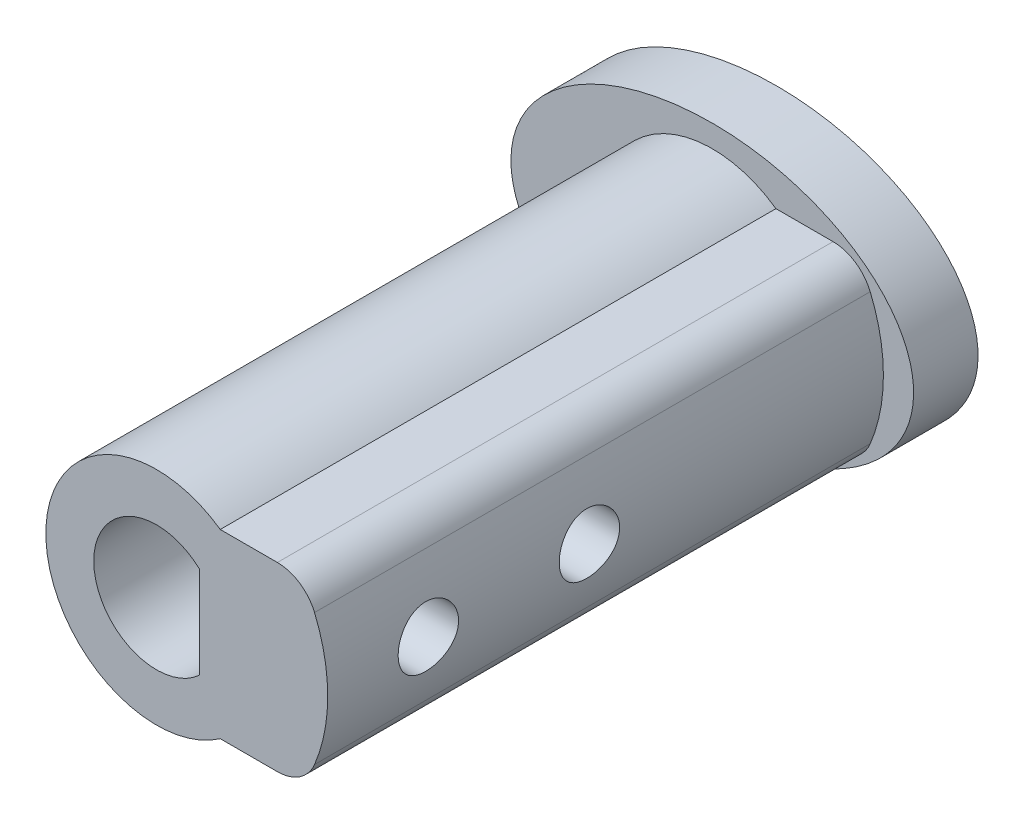
SolidWorks part; units mm, degrees
ref_plane "Front Plane" through (0, 0, 0) normal (0, 0, 1) x (1, 0, 0)
ref_plane "Top Plane" through (0, 0, 0) normal (0, 1, 0) x (1, 0, 0)
ref_plane "Right Plane" through (0, 0, 0) normal (1, 0, 0) x (0, 0, -1)
sketch "Sketch1" plane through (0, 0, 0) normal (0, 0, 1) x (1, 0, 0)
  line L7 (4.25, -2.25) -> (-4.25, -2.25)
  line L8 (4.25, -2.25) -> (4.25, 2.25)
  line L9 (4.25, 2.25) -> (-4.25, 2.25)
  line L10 (-4.25, -2.25) -> (-4.25, 2.25)
  line L11 (4.25, -2.25) -> (-4.25, 2.25) construction
  line L12 (4.25, 2.25) -> (-4.25, -2.25) construction
  circle A0 centre (0, 0) radius 2.75
  circle A1 centre (0, 0) radius 4.25
  dimension "D1" = 5.5
  dimension "D2" = 8.5
  dimension "D4" = 4.5
extrude "Boss-Extrude1" add sketch "Sketch1" along normal blind 13.8 contours A1 L9 A0 L7 | A0 region at (3.1989, 0, 0)
sketch "Sketch3" plane through (0, 0, 13.8) normal (0, 0, 1) x (1, 0, 0)
  line L0 (1, 1.118) -> (1, -1.118)
  circle A1 centre (0, 0) radius 1.5
  dimension "D1" = 3
  dimension "D2" = 1
extrude "Cut-Extrude1" cut sketch "Sketch3" against normal blind 8.3 contours L0 A1 region at (-0.148, 0, 13.8)
ref_plane "Plane1" through (4.25, 0, 0) normal (1, 0, 0) x (0, 0, -1)
sketch "Sketch5" plane through (4.25, 0, 0) normal (1, 0, 0) x (0, 0, -1)
  line L1 (-13.8, 2.25) -> (-13.8, -2.25) construction
  circle A0 centre (-11.3, 0) radius 0.75
  circle A1 centre (-7.3, 0) radius 0.75
  dimension "D1" = 1.5
  dimension "D2" = 1.5
  dimension "D3" = 2.5
  dimension "D4" = 6.5
extrude "Cut-Extrude3" cut sketch "Sketch5" against normal blind 4.5
sketch "Sketch4" plane through (0, 0, 0) normal (0, 0, -1) x (-1, 0, 0)
  line L2 (-3.6056, -2.25) -> (-1.5811, -2.25)
  line L3 (-1.5811, 2.25) -> (-3.6056, 2.25)
  line L4 (-3.6056, -2.25) -> (-1.5811, -2.25)
  line L5 (-1.5811, 2.25) -> (-3.6056, 2.25)
  circle A0 centre (0, 0) radius 4
  arc A3 (-3.6056, 2.25) -> (-3.6056, -2.25) centre (0, 0) ccw
  arc A4 (-1.5811, -2.25) -> (-1.5811, 2.25) centre (0, 0) ccw
  arc A5 (-3.6056, 2.25) -> (-3.6056, -2.25) centre (0, 0) ccw
  arc A6 (-1.5811, -2.25) -> (-1.5811, 2.25) centre (0, 0) ccw
  dimension "D2" = 8
  dimension "D1" = 0
extrude "Boss-Extrude3" [suppressed] add sketch "Sketch4" along normal blind 2
sketch "Sketch7" plane through (0, 0, 0) normal (0, 0, -1) x (-1, 0, 0)
  ellipse E0 centre (0, 0) end of major axis (5, 0) minor radius 3.3
  dimension "D1" = 6.6
  dimension "D2" = 10
extrude "Boss-Extrude5" add sketch "Sketch7" along normal blind 1.6
fillet "Fillet1" radius 1 2 edges at (3.6056, -2.25, 6.9) (3.6056, 2.25, 6.9)
sketch "Sketch8" plane through (0, 0, 13.8) normal (0, 0, 1) x (1, 0, 0)
  line L0 (1, 1.118) -> (1, -1.118) construction
  line L1 (1, 1.118) -> (1, -1.118)
  line L2 (1.06, 1.1446) -> (1.06, -1.1446)
  arc A0 (1, 1.118) -> (1, -1.118) centre (0, 0) ccw construction
  arc A1 (1, 1.118) -> (1, -1.118) centre (0, 0) ccw
  arc A2 (1.06, 1.1446) -> (1.06, -1.1446) centre (0, 0) ccw
  dimension "D1" = 0.06
extrude "Cut-Extrude4" cut sketch "Sketch8" against normal up to surface (8.3 mm away) up to face at (-0.25, 0, 5.5)
